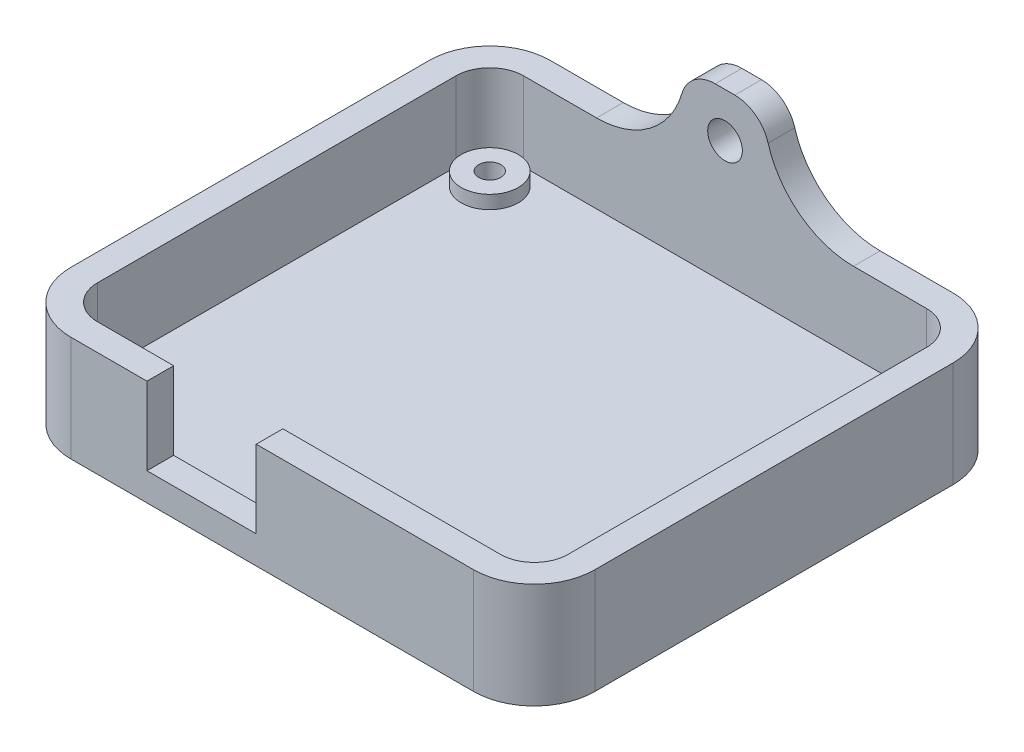
SolidWorks part; units mm, degrees
ref_plane "Front Plane" through (0, 0, 0) normal (0, 0, 1) x (1, 0, 0)
ref_plane "Top Plane" through (0, 0, 0) normal (0, 1, 0) x (1, 0, 0)
ref_plane "Right Plane" through (0, 0, 0) normal (1, 0, 0) x (0, 0, -1)
sketch "Sketch1" plane through (0, 0, 0) normal (0, 1, 0) x (1, 0, 0)
  line L0 (3.81, 3) -> (49.09, 3)
  line L1 (3.81, 0) -> (49.09, 0)
  line L2 (0, -3.81) -> (0, -44.09)
  line L3 (3.81, -47.9) -> (49.09, -47.9)
  line L4 (52.9, -3.81) -> (52.9, -44.09)
  line L5 (55.9, -3.81) -> (55.9, -44.09)
  line L6 (3.81, -50.9) -> (49.09, -50.9)
  line L7 (-3, -3.81) -> (-3, -44.09)
  arc A0 (52.9, -3.81) -> (49.09, 0) centre (49.09, -3.81) ccw
  arc A1 (0, -3.81) -> (3.81, 0) centre (3.81, -3.81) cw
  arc A2 (3.81, -47.9) -> (0, -44.09) centre (3.81, -44.09) cw
  arc A3 (52.9, -44.09) -> (49.09, -47.9) centre (49.09, -44.09) cw
  circle A4 centre (49.09, -44.09) radius 1.25
  circle A5 centre (3.81, -44.09) radius 1.25
  circle A6 centre (3.81, -3.81) radius 1.25
  circle A7 centre (49.09, -3.81) radius 1.25
  arc A8 (55.9, -3.81) -> (49.09, 3) centre (49.09, -3.81) ccw
  arc A9 (55.9, -44.09) -> (49.09, -50.9) centre (49.09, -44.09) cw
  arc A10 (3.81, -50.9) -> (-3, -44.09) centre (3.81, -44.09) cw
  arc A11 (-3, -3.81) -> (3.81, 3) centre (3.81, -3.81) cw
  circle A12 centre (3.81, -3.81) radius 3.21
  circle A13 centre (49.09, -3.81) radius 3.21
  circle A14 centre (49.09, -44.09) radius 3.21
  circle A15 centre (3.81, -44.09) radius 3.21
  point P7 (52.9, 0)
  point P10 (0, 0)
  point P15 (52.9, -47.9)
  dimension "D3" = 3.81
  dimension "D4" = 3.81
  dimension "D5" = 3.81
  dimension "D6" = 3.81
  dimension "D7" = 3
  dimension "D8" = 2.5
  dimension "D9" = 2.5
  dimension "D10" = 2.5
  dimension "D11" = 2.5
  dimension "D12" = 6.42
  dimension "D13" = 6.42
  dimension "D14" = 6.42
  dimension "D15" = 6.42
  dimension "D1" = 52.9
  dimension "D2" = 47.9
extrude "Boss-Extrude1" add sketch "Sketch1" against normal blind 3 contours L7 A10 L6 A9 L5 A8 L0 A11
extrude "Cut-Extrude1" cut sketch "Sketch1<3>" against normal up to next contours A6 | A5 | A4 | A7 region at (49.09, 0, 44.09) region at (3.81, 0, 44.09) region at (3.81, 0, 3.81) region at (49.09, 0, 3.81)
sketch "Sketch1<3>" plane through (0, 0, 0) normal (0, 1, 0) x (1, 0, 0) same geometry as "Sketch1"
extrude "Boss-Extrude2" add sketch "Sketch1<4>" along normal blind 8.86 contours A11 L7 A10 L6 A9 L5 A8 L0 L4 A3 L3 A2 L2 A1 L1 A0 region at (26.45, 0, -2.2016)
sketch "Sketch1<4>" plane through (0, 0, 0) normal (0, 1, 0) x (1, 0, 0) same geometry as "Sketch1"
extrude "Boss-Extrude3" add sketch "Sketch1<5>" along normal blind 1.5 contours A13 A7 | A14 A4 | A15 A5 | A12 A6 region at (0.6908, 0, 3.81) region at (45.9708, 0, 3.81) region at (45.9708, 0, 44.09) region at (0.6908, 0, 44.09)
sketch "Sketch1<5>" plane through (0, 0, 0) normal (0, 1, 0) x (1, 0, 0) same geometry as "Sketch1"
sketch "Sketch2" plane through (0, 0, 50.9) normal (0, 0, 1) x (1, 0, 0)
  line L0 (3.81, -3) -> (49.09, -3) construction
  line L1 (12.36, 8.865) -> (24.64, 8.865)
  line L2 (12.36, 8.865) -> (12.36, 0.135)
  line L3 (12.36, 0.135) -> (24.64, 0.135)
  line L4 (24.64, 8.865) -> (24.64, 0.135)
  line L5 (-3, -3) -> (-3, 8.86) construction
  dimension "D1" = 3.135
  dimension "D2" = 8.73
  dimension "D3" = 12.28
  dimension "D4" = 15.36
extrude "Cut-Extrude2" cut sketch "Sketch2" against normal blind 3
sketch "Sketch5" plane through (0, 0, -3) normal (0, 0, -1) x (-1, 0, 0)
  line L0 (-3.81, 8.86) -> (-49.09, 8.86) construction
  line L1 (-31.45, 8.86) -> (-21.45, 8.86)
  line L2 (-31.45, 8.86) -> (-31.45, 14.96)
  line L3 (-27.55, 18.86) -> (-25.35, 18.86)
  line L4 (-21.45, 8.86) -> (-21.45, 14.96)
  line L5 (-55.9, -3) -> (-55.9, 8.86) construction
  arc A0 (-31.45, 14.96) -> (-27.55, 18.86) centre (-27.55, 14.96) cw
  arc A1 (-21.45, 14.96) -> (-25.35, 18.86) centre (-25.35, 14.96) ccw
  circle A2 centre (-26.45, 13.86) radius 1.95
  point P8 (-31.45, 18.86)
  point P11 (-21.45, 18.86)
  dimension "D3" = 3.9
  dimension "D4" = 3.9
  dimension "D6" = 3.9
  dimension "D1" = 10
  dimension "D2" = 10
  dimension "D5" = 24.45
  dimension "D7" = 5
  dimension "D8" = 5
extrude "Boss-Extrude5" add sketch "Sketch5" against normal blind 3
fillet "Fillet1" radius 10 2 edges at (21.45, 8.86, -1.5) (31.45, 8.86, -1.5)
